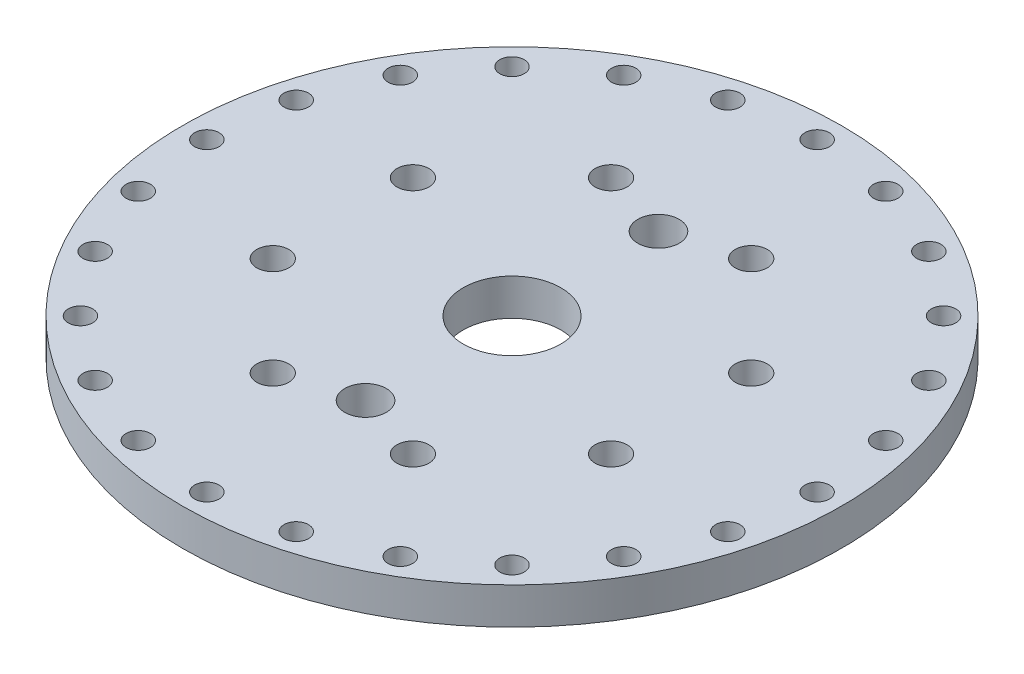
SolidWorks part; units mm, degrees
material "Alloy Steel"
ref_plane "Front Plane" through (0, 0, 0) normal (0, 0, 1) x (1, 0, 0)
ref_plane "Top Plane" through (0, 0, 0) normal (0, 1, 0) x (1, 0, 0)
ref_plane "Right Plane" through (0, 0, 0) normal (1, 0, 0) x (0, 0, -1)
sketch "Sketch5" plane through (0, 0, 0) normal (0, 1, 0) x (1, 0, 0)
  line L0 (87.3464, 51.4964) -> (89.0397, 50.8872)
  line L1 (89.0397, 50.8872) -> (90.7249, 50.062)
  line L2 (90.7249, 50.062) -> (90.7249, 49.095)
  line L3 (90.7249, 49.095) -> (89.0397, 48.2698)
  line L4 (89.0397, 48.2698) -> (87.3464, 47.6606)
  line L5 (87.3464, 47.6606) -> (87.2693, 46.4828)
  line L6 (87.2693, 46.4828) -> (88.8685, 45.6578)
  line L7 (88.8685, 45.6578) -> (90.4317, 44.6196)
  line L8 (90.4317, 44.6196) -> (90.3054, 43.6609)
  line L9 (90.3054, 43.6609) -> (88.5268, 43.0627)
  line L10 (88.5268, 43.0627) -> (86.7686, 42.6797)
  line L11 (86.7686, 42.6797) -> (86.5383, 41.5221)
  line L12 (86.5383, 41.5221) -> (88.0162, 40.4955)
  line L13 (88.0162, 40.4955) -> (89.4304, 39.2621)
  line L14 (89.4304, 39.2621) -> (89.1801, 38.328)
  line L15 (89.1801, 38.328) -> (87.3386, 37.9672)
  line L16 (87.3386, 37.9672) -> (85.5454, 37.8169)
  line L17 (85.5454, 37.8169) -> (85.1661, 36.6994)
  line L18 (85.1661, 36.6994) -> (86.4974, 35.4884)
  line L19 (86.4974, 35.4884) -> (87.7385, 34.0811)
  line L20 (87.7385, 34.0811) -> (87.3685, 33.1877)
  line L21 (87.3685, 33.1877) -> (85.4956, 33.0702)
  line L22 (85.4956, 33.0702) -> (83.6981, 33.1553)
  line L23 (83.6981, 33.1553) -> (83.1762, 32.0968)
  line L24 (83.1762, 32.0968) -> (84.3379, 30.7226)
  line L25 (84.3379, 30.7226) -> (85.3848, 29.1653)
  line L26 (85.3848, 29.1653) -> (84.9013, 28.3278)
  line L27 (84.9013, 28.3278) -> (83.0292, 28.4557)
  line L28 (83.0292, 28.4557) -> (81.2581, 28.7747)
  line L29 (81.2581, 28.7747) -> (80.6024, 27.7935)
  line L30 (80.6024, 27.7935) -> (81.575, 26.2794)
  line L31 (81.575, 26.2794) -> (82.4096, 24.5987)
  line L32 (82.4096, 24.5987) -> (81.821, 23.8315)
  line L33 (81.821, 23.8315) -> (79.9815, 24.2028)
  line L34 (79.9815, 24.2028) -> (78.2673, 24.7502)
  line L35 (78.2673, 24.7502) -> (77.4891, 23.8628)
  line L36 (77.4891, 23.8628) -> (78.2556, 22.2348)
  line L37 (78.2556, 22.2348) -> (78.8638, 20.4595)
  line L38 (78.8638, 20.4595) -> (78.18, 19.7757)
  line L39 (78.18, 19.7757) -> (76.4047, 20.3839)
  line L40 (76.4047, 20.3839) -> (74.7767, 21.1504)
  line L41 (74.7767, 21.1504) -> (73.8893, 20.3722)
  line L42 (73.8893, 20.3722) -> (74.4368, 18.658)
  line L43 (74.4368, 18.658) -> (74.808, 16.8186)
  line L44 (74.808, 16.8186) -> (74.0408, 16.2299)
  line L45 (74.0408, 16.2299) -> (72.3602, 17.0645)
  line L46 (72.3602, 17.0645) -> (70.846, 18.0371)
  line L47 (70.846, 18.0371) -> (69.8648, 17.3814)
  line L48 (69.8648, 17.3814) -> (70.1838, 15.6104)
  line L49 (70.1838, 15.6104) -> (70.3117, 13.7382)
  line L50 (70.3117, 13.7382) -> (69.4742, 13.2547)
  line L51 (69.4742, 13.2547) -> (67.9169, 14.3016)
  line L52 (67.9169, 14.3016) -> (66.5427, 15.4634)
  line L53 (66.5427, 15.4634) -> (65.4842, 14.9415)
  line L54 (65.4842, 14.9415) -> (65.5693, 13.1439)
  line L55 (65.5693, 13.1439) -> (65.4518, 11.271)
  line L56 (65.4518, 11.271) -> (64.5584, 10.901)
  line L57 (64.5584, 10.901) -> (63.1511, 12.1422)
  line L58 (63.1511, 12.1422) -> (61.9401, 13.4734)
  line L59 (61.9401, 13.4734) -> (60.8226, 13.0941)
  line L60 (60.8226, 13.0941) -> (60.6724, 11.3009)
  line L61 (60.6724, 11.3009) -> (60.3115, 9.4594)
  line L62 (60.3115, 9.4594) -> (59.3774, 9.2091)
  line L63 (59.3774, 9.2091) -> (58.144, 10.6233)
  line L64 (58.144, 10.6233) -> (57.1174, 12.1012)
  line L65 (57.1174, 12.1012) -> (55.9598, 11.8709)
  line L66 (55.9598, 11.8709) -> (55.5768, 10.1127)
  line L67 (55.5768, 10.1127) -> (54.9786, 8.3341)
  line L68 (54.9786, 8.3341) -> (54.0199, 8.2078)
  line L69 (54.0199, 8.2078) -> (52.9817, 9.771)
  line L70 (52.9817, 9.771) -> (52.1567, 11.3702)
  line L71 (52.1567, 11.3702) -> (50.979, 11.2931)
  line L72 (50.979, 11.2931) -> (50.3698, 9.5998)
  line L73 (50.3698, 9.5998) -> (49.5446, 7.9146)
  line L74 (49.5446, 7.9146) -> (48.5775, 7.9146)
  line L75 (48.5775, 7.9146) -> (47.7523, 9.5998)
  line L76 (47.7523, 9.5998) -> (47.1431, 11.2931)
  line L77 (47.1431, 11.2931) -> (45.9654, 11.3702)
  line L78 (45.9654, 11.3702) -> (45.1403, 9.771)
  line L79 (45.1403, 9.771) -> (44.1021, 8.2078)
  line L80 (44.1021, 8.2078) -> (43.1434, 8.3341)
  line L81 (43.1434, 8.3341) -> (42.5452, 10.1127)
  line L82 (42.5452, 10.1127) -> (42.1622, 11.8709)
  line L83 (42.1622, 11.8709) -> (41.0046, 12.1012)
  line L84 (41.0046, 12.1012) -> (39.978, 10.6233)
  line L85 (39.978, 10.6233) -> (38.7447, 9.2091)
  line L86 (38.7447, 9.2091) -> (37.8106, 9.4594)
  line L87 (37.8106, 9.4594) -> (37.4497, 11.3009)
  line L88 (37.4497, 11.3009) -> (37.2994, 13.0941)
  line L89 (37.2994, 13.0941) -> (36.1819, 13.4734)
  line L90 (36.1819, 13.4734) -> (34.9709, 12.1422)
  line L91 (34.9709, 12.1422) -> (33.5636, 10.901)
  line L92 (33.5636, 10.901) -> (32.6702, 11.271)
  line L93 (32.6702, 11.271) -> (32.5527, 13.1439)
  line L94 (32.5527, 13.1439) -> (32.6378, 14.9415)
  line L95 (32.6378, 14.9415) -> (31.5793, 15.4634)
  line L96 (31.5793, 15.4634) -> (30.2051, 14.3016)
  line L97 (30.2051, 14.3016) -> (28.6478, 13.2547)
  line L98 (28.6478, 13.2547) -> (27.8103, 13.7382)
  line L99 (27.8103, 13.7382) -> (27.9382, 15.6104)
  line L100 (27.9382, 15.6104) -> (28.2572, 17.3814)
  line L101 (28.2572, 17.3814) -> (27.276, 18.0371)
  line L102 (27.276, 18.0371) -> (25.7619, 17.0645)
  line L103 (25.7619, 17.0645) -> (24.0812, 16.2299)
  line L104 (24.0812, 16.2299) -> (23.314, 16.8186)
  line L105 (23.314, 16.8186) -> (23.6853, 18.658)
  line L106 (23.6853, 18.658) -> (24.2327, 20.3722)
  line L107 (24.2327, 20.3722) -> (23.3453, 21.1504)
  line L108 (23.3453, 21.1504) -> (21.7173, 20.3839)
  line L109 (21.7173, 20.3839) -> (19.9421, 19.7757)
  line L110 (19.9421, 19.7757) -> (19.2582, 20.4595)
  line L111 (19.2582, 20.4595) -> (19.8664, 22.2348)
  line L112 (19.8664, 22.2348) -> (20.6329, 23.8628)
  line L113 (20.6329, 23.8628) -> (19.8547, 24.7502)
  line L114 (19.8547, 24.7502) -> (18.1405, 24.2028)
  line L115 (18.1405, 24.2028) -> (16.3011, 23.8315)
  line L116 (16.3011, 23.8315) -> (15.7124, 24.5987)
  line L117 (15.7124, 24.5987) -> (16.547, 26.2794)
  line L118 (16.547, 26.2794) -> (17.5196, 27.7935)
  line L119 (17.5196, 27.7935) -> (16.8639, 28.7747)
  line L120 (16.8639, 28.7747) -> (15.0929, 28.4557)
  line L121 (15.0929, 28.4557) -> (13.2207, 28.3278)
  line L122 (13.2207, 28.3278) -> (12.7372, 29.1653)
  line L123 (12.7372, 29.1653) -> (13.7841, 30.7226)
  line L124 (13.7841, 30.7226) -> (14.9459, 32.0968)
  line L125 (14.9459, 32.0968) -> (14.424, 33.1553)
  line L126 (14.424, 33.1553) -> (12.6264, 33.0702)
  line L127 (12.6264, 33.0702) -> (10.7535, 33.1877)
  line L128 (10.7535, 33.1877) -> (10.3835, 34.0811)
  line L129 (10.3835, 34.0811) -> (11.6247, 35.4884)
  line L130 (11.6247, 35.4884) -> (12.9559, 36.6994)
  line L131 (12.9559, 36.6994) -> (12.5766, 37.8169)
  line L132 (12.5766, 37.8169) -> (10.7834, 37.9672)
  line L133 (10.7834, 37.9672) -> (8.9419, 38.328)
  line L134 (8.9419, 38.328) -> (8.6916, 39.2621)
  line L135 (8.6916, 39.2621) -> (10.1058, 40.4955)
  line L136 (10.1058, 40.4955) -> (11.5837, 41.5221)
  line L137 (11.5837, 41.5221) -> (11.3534, 42.6797)
  line L138 (11.3534, 42.6797) -> (9.5952, 43.0627)
  line L139 (9.5952, 43.0627) -> (7.8167, 43.6609)
  line L140 (7.8167, 43.6609) -> (7.6903, 44.6196)
  line L141 (7.6903, 44.6196) -> (9.2536, 45.6578)
  line L142 (9.2536, 45.6578) -> (10.8528, 46.4828)
  line L143 (10.8528, 46.4828) -> (10.7757, 47.6606)
  line L144 (10.7757, 47.6606) -> (9.0823, 48.2698)
  line L145 (9.0823, 48.2698) -> (7.3971, 49.095)
  line L146 (7.3971, 49.095) -> (7.3971, 50.062)
  line L147 (7.3971, 50.062) -> (9.0823, 50.8872)
  line L148 (9.0823, 50.8872) -> (10.7757, 51.4964)
  line L149 (10.7757, 51.4964) -> (10.8528, 52.6742)
  line L150 (10.8528, 52.6742) -> (9.2536, 53.4992)
  line L151 (9.2536, 53.4992) -> (7.6903, 54.5374)
  line L152 (7.6903, 54.5374) -> (7.8167, 55.4961)
  line L153 (7.8167, 55.4961) -> (9.5952, 56.0943)
  line L154 (9.5952, 56.0943) -> (11.3534, 56.4773)
  line L155 (11.3534, 56.4773) -> (11.5837, 57.6349)
  line L156 (11.5837, 57.6349) -> (10.1058, 58.6615)
  line L157 (10.1058, 58.6615) -> (8.6916, 59.8949)
  line L158 (8.6916, 59.8949) -> (8.9419, 60.829)
  line L159 (8.9419, 60.829) -> (10.7834, 61.1898)
  line L160 (10.7834, 61.1898) -> (12.5766, 61.3401)
  line L161 (12.5766, 61.3401) -> (12.9559, 62.4576)
  line L162 (12.9559, 62.4576) -> (11.6247, 63.6686)
  line L163 (11.6247, 63.6686) -> (10.3835, 65.0759)
  line L164 (10.3835, 65.0759) -> (10.7535, 65.9693)
  line L165 (10.7535, 65.9693) -> (12.6264, 66.0868)
  line L166 (12.6264, 66.0868) -> (14.424, 66.0017)
  line L167 (14.424, 66.0017) -> (14.9459, 67.0602)
  line L168 (14.9459, 67.0602) -> (13.7841, 68.4344)
  line L169 (13.7841, 68.4344) -> (12.7372, 69.9917)
  line L170 (12.7372, 69.9917) -> (13.2207, 70.8292)
  line L171 (13.2207, 70.8292) -> (15.0929, 70.7013)
  line L172 (15.0929, 70.7013) -> (16.8639, 70.3823)
  line L173 (16.8639, 70.3823) -> (17.5196, 71.3635)
  line L174 (17.5196, 71.3635) -> (16.547, 72.8776)
  line L175 (16.547, 72.8776) -> (15.7124, 74.5583)
  line L176 (15.7124, 74.5583) -> (16.3011, 75.3255)
  line L177 (16.3011, 75.3255) -> (18.1405, 74.9542)
  line L178 (18.1405, 74.9542) -> (19.8547, 74.4068)
  line L179 (19.8547, 74.4068) -> (20.6329, 75.2942)
  line L180 (20.6329, 75.2942) -> (19.8664, 76.9222)
  line L181 (19.8664, 76.9222) -> (19.2582, 78.6975)
  line L182 (19.2582, 78.6975) -> (19.9421, 79.3813)
  line L183 (19.9421, 79.3813) -> (21.7173, 78.7731)
  line L184 (21.7173, 78.7731) -> (23.3453, 78.0066)
  line L185 (23.3453, 78.0066) -> (24.2327, 78.7848)
  line L186 (24.2327, 78.7848) -> (23.6853, 80.499)
  line L187 (23.6853, 80.499) -> (23.314, 82.3384)
  line L188 (23.314, 82.3384) -> (24.0812, 82.9271)
  line L189 (24.0812, 82.9271) -> (25.7619, 82.0925)
  line L190 (25.7619, 82.0925) -> (27.276, 81.1199)
  line L191 (27.276, 81.1199) -> (28.2572, 81.7756)
  line L192 (28.2572, 81.7756) -> (27.9382, 83.5466)
  line L193 (27.9382, 83.5466) -> (27.8103, 85.4188)
  line L194 (27.8103, 85.4188) -> (28.6478, 85.9023)
  line L195 (28.6478, 85.9023) -> (30.2051, 84.8554)
  line L196 (30.2051, 84.8554) -> (31.5793, 83.6936)
  line L197 (31.5793, 83.6936) -> (32.6378, 84.2155)
  line L198 (32.6378, 84.2155) -> (32.5527, 86.0131)
  line L199 (32.5527, 86.0131) -> (32.6702, 87.886)
  line L200 (32.6702, 87.886) -> (33.5636, 88.256)
  line L201 (33.5636, 88.256) -> (34.9709, 87.0148)
  line L202 (34.9709, 87.0148) -> (36.1819, 85.6836)
  line L203 (36.1819, 85.6836) -> (37.2994, 86.0629)
  line L204 (37.2994, 86.0629) -> (37.4497, 87.8561)
  line L205 (37.4497, 87.8561) -> (37.8106, 89.6976)
  line L206 (37.8106, 89.6976) -> (38.7447, 89.9479)
  line L207 (38.7447, 89.9479) -> (39.978, 88.5337)
  line L208 (39.978, 88.5337) -> (41.0046, 87.0558)
  line L209 (41.0046, 87.0558) -> (42.1622, 87.2861)
  line L210 (42.1622, 87.2861) -> (42.5452, 89.0443)
  line L211 (42.5452, 89.0443) -> (43.1434, 90.8228)
  line L212 (43.1434, 90.8228) -> (44.1021, 90.9492)
  line L213 (44.1021, 90.9492) -> (45.1403, 89.386)
  line L214 (45.1403, 89.386) -> (45.9654, 87.7868)
  line L215 (45.9654, 87.7868) -> (47.1431, 87.8639)
  line L216 (47.1431, 87.8639) -> (47.7523, 89.5572)
  line L217 (47.7523, 89.5572) -> (48.5775, 91.2424)
  line L218 (48.5775, 91.2424) -> (49.5446, 91.2424)
  line L219 (49.5446, 91.2424) -> (50.3698, 89.5572)
  line L220 (50.3698, 89.5572) -> (50.979, 87.8639)
  line L221 (50.979, 87.8639) -> (52.1567, 87.7868)
  line L222 (52.1567, 87.7868) -> (52.9817, 89.386)
  line L223 (52.9817, 89.386) -> (54.0199, 90.9492)
  line L224 (54.0199, 90.9492) -> (54.9786, 90.8228)
  line L225 (54.9786, 90.8228) -> (55.5768, 89.0443)
  line L226 (55.5768, 89.0443) -> (55.9598, 87.2861)
  line L227 (55.9598, 87.2861) -> (57.1174, 87.0558)
  line L228 (57.1174, 87.0558) -> (58.144, 88.5337)
  line L229 (58.144, 88.5337) -> (59.3774, 89.9479)
  line L230 (59.3774, 89.9479) -> (60.3115, 89.6976)
  line L231 (60.3115, 89.6976) -> (60.6724, 87.8561)
  line L232 (60.6724, 87.8561) -> (60.8226, 86.0629)
  line L233 (60.8226, 86.0629) -> (61.9401, 85.6836)
  line L234 (61.9401, 85.6836) -> (63.1511, 87.0148)
  line L235 (63.1511, 87.0148) -> (64.5584, 88.256)
  line L236 (64.5584, 88.256) -> (65.4518, 87.886)
  line L237 (65.4518, 87.886) -> (65.5693, 86.0131)
  line L238 (65.5693, 86.0131) -> (65.4842, 84.2155)
  line L239 (65.4842, 84.2155) -> (66.5427, 83.6936)
  line L240 (66.5427, 83.6936) -> (67.9169, 84.8554)
  line L241 (67.9169, 84.8554) -> (69.4742, 85.9023)
  line L242 (69.4742, 85.9023) -> (70.3117, 85.4188)
  line L243 (70.3117, 85.4188) -> (70.1838, 83.5466)
  line L244 (70.1838, 83.5466) -> (69.8648, 81.7756)
  line L245 (69.8648, 81.7756) -> (70.846, 81.1199)
  line L246 (70.846, 81.1199) -> (72.3602, 82.0925)
  line L247 (72.3602, 82.0925) -> (74.0408, 82.9271)
  line L248 (74.0408, 82.9271) -> (74.808, 82.3384)
  line L249 (74.808, 82.3384) -> (74.4368, 80.499)
  line L250 (74.4368, 80.499) -> (73.8893, 78.7848)
  line L251 (73.8893, 78.7848) -> (74.7767, 78.0066)
  line L252 (74.7767, 78.0066) -> (76.4047, 78.7731)
  line L253 (76.4047, 78.7731) -> (78.18, 79.3813)
  line L254 (78.18, 79.3813) -> (78.8638, 78.6975)
  line L255 (78.8638, 78.6975) -> (78.2556, 76.9222)
  line L256 (78.2556, 76.9222) -> (77.4891, 75.2942)
  line L257 (77.4891, 75.2942) -> (78.2673, 74.4068)
  line L258 (78.2673, 74.4068) -> (79.9815, 74.9542)
  line L259 (79.9815, 74.9542) -> (81.821, 75.3255)
  line L260 (81.821, 75.3255) -> (82.4096, 74.5583)
  line L261 (82.4096, 74.5583) -> (81.575, 72.8776)
  line L262 (81.575, 72.8776) -> (80.6024, 71.3635)
  line L263 (80.6024, 71.3635) -> (81.2581, 70.3823)
  line L264 (81.2581, 70.3823) -> (83.0292, 70.7013)
  line L265 (83.0292, 70.7013) -> (84.9013, 70.8292)
  line L266 (84.9013, 70.8292) -> (85.3848, 69.9917)
  line L267 (85.3848, 69.9917) -> (84.3379, 68.4344)
  line L268 (84.3379, 68.4344) -> (83.1762, 67.0602)
  line L269 (83.1762, 67.0602) -> (83.6981, 66.0017)
  line L270 (83.6981, 66.0017) -> (85.4956, 66.0868)
  line L271 (85.4956, 66.0868) -> (87.3685, 65.9693)
  line L272 (87.3685, 65.9693) -> (87.7385, 65.0759)
  line L273 (87.7385, 65.0759) -> (86.4974, 63.6686)
  line L274 (86.4974, 63.6686) -> (85.1661, 62.4576)
  line L275 (85.1661, 62.4576) -> (85.5454, 61.3401)
  line L276 (85.5454, 61.3401) -> (87.3386, 61.1898)
  line L277 (87.3386, 61.1898) -> (89.1801, 60.829)
  line L278 (89.1801, 60.829) -> (89.4304, 59.8949)
  line L279 (89.4304, 59.8949) -> (88.0162, 58.6615)
  line L280 (88.0162, 58.6615) -> (86.5383, 57.6349)
  line L281 (86.5383, 57.6349) -> (86.7686, 56.4773)
  line L282 (86.7686, 56.4773) -> (88.5268, 56.0943)
  line L283 (88.5268, 56.0943) -> (90.3054, 55.4961)
  line L284 (90.3054, 55.4961) -> (90.4317, 54.5374)
  line L285 (90.4317, 54.5374) -> (88.8685, 53.4992)
  line L286 (88.8685, 53.4992) -> (87.2693, 52.6742)
  line L287 (87.2693, 52.6742) -> (87.3464, 51.4964)
  line L288 (49.061, 91.2424) -> (49.061, 7.9146) construction
  line L289 (7.3971, 49.5785) -> (90.7249, 49.5785) construction
  point P292 (49.061, 49.5785)
sketch "Sketch6" plane through (0, 0, 0) normal (0, 1, 0) x (1, 0, 0)
  line L0 (49.061, 91.2424) -> (49.061, 7.9146) construction
  circle A0 centre (49.061, 49.5785) radius 4
  dimension "D1" = 8
sketch "Sketch7" plane through (0, 0, 0) normal (0, 1, 0) x (1, 0, 0)
  line L0 (49.061, 91.2424) -> (49.061, 7.9146) construction
  line L1 (25.4921, 49.5785) -> (64.6594, 49.5785) construction
  line L2 (7.3971, 49.5785) -> (90.7249, 49.5785) construction
  circle A0 centre (49.061, 61.5785) radius 1.7
  circle A1 centre (49.061, 37.5785) radius 1.7
  dimension "D2" = 3.4
  dimension "D1" = 12
sketch "Sketch8" plane through (0, 0, 0) normal (0, 1, 0) x (1, 0, 0)
  line L0 (7.3971, 49.5785) -> (90.7249, 49.5785) construction
  circle A0 centre (49.061, 49.5785) radius 27
  dimension "D1" = 54
sketch "Sketch9" plane through (0, 0, 0) normal (0, 1, 0) x (1, 0, 0)
  line L0 (49.061, 91.2424) -> (49.061, 7.9146) construction
  line L1 (49.061, 74.5785) -> (49.061, 76.5785) construction
  circle A0 centre (49.061, 74.5785) radius 1
  circle A1 centre (49.061, 49.5785) radius 27 construction
  circle A2 centre (55.5315, 73.7266) radius 1
  circle A3 centre (61.561, 71.2291) radius 1
  circle A4 centre (66.7387, 67.2562) radius 1
  circle A5 centre (70.7116, 62.0785) radius 1
  circle A6 centre (73.2092, 56.049) radius 1
  circle A7 centre (74.061, 49.5785) radius 1
  circle A8 centre (73.2092, 43.108) radius 1
  circle A9 centre (70.7116, 37.0785) radius 1
  circle A10 centre (66.7387, 31.9008) radius 1
  circle A11 centre (61.561, 27.9279) radius 1
  circle A12 centre (55.5315, 25.4304) radius 1
  circle A13 centre (49.061, 24.5785) radius 1
  circle A14 centre (42.5905, 25.4304) radius 1
  circle A15 centre (36.561, 27.9279) radius 1
  circle A16 centre (31.3833, 31.9008) radius 1
  circle A17 centre (27.4104, 37.0785) radius 1
  circle A18 centre (24.9129, 43.108) radius 1
  circle A19 centre (24.061, 49.5785) radius 1
  circle A20 centre (24.9129, 56.049) radius 1
  circle A21 centre (27.4104, 62.0785) radius 1
  circle A22 centre (31.3833, 67.2562) radius 1
  circle A23 centre (36.561, 71.2291) radius 1
  circle A24 centre (42.5905, 73.7266) radius 1
  point P55 (49.061, 49.5785)
  dimension "D1" = 2
  dimension "D2" = 2
  dimension "D3" = 24
extrude "Boss-Extrude1" add sketch "Sketch8" along normal blind 3
extrude "Boss-Extrude2" [suppressed] add sketch "Sketch5" along normal up to surface (4 mm away) up to face at (49.061, 3, -22.5785)
extrude "Cut-Extrude1" cut sketch "Sketch6" along normal up to next
extrude "Cut-Extrude2" cut sketch "Sketch7" along normal up to next
extrude "Cut-Extrude3" cut sketch "Sketch9" along normal up to next
ref_axis "Axis1" [suppressed] through (49.061, 4, -49.5785) along (0, -1, 0)
sketch "Sketch11" plane through (0, 0, 0) normal (0, 1, 0) x (1, 0, 0)
  line L0 (59.3935, 74.5232) -> (49.061, 49.5785) construction
  line L1 (49.061, 49.5785) -> (49.061, 76.5785) construction
  circle A0 centre (49.061, 49.5785) radius 27 construction
  circle A1 centre (54.8013, 63.4367) radius 1.3125
  circle A2 centre (62.9192, 55.3188) radius 1.3125
  circle A3 centre (62.9192, 43.8382) radius 1.3125
  circle A4 centre (54.8013, 35.7203) radius 1.3125
  circle A5 centre (43.3208, 35.7203) radius 1.3125
  circle A6 centre (35.2028, 43.8382) radius 1.3125
  circle A7 centre (35.2028, 55.3188) radius 1.3125
  circle A8 centre (43.3208, 63.4367) radius 1.3125
  point P0 (49.061, 49.5785)
  point P36 (49.061, 49.5785)
  dimension "D2" = 2.625
  dimension "D1" = 15
  dimension "D4" = 22.5
  dimension "D3" = 8
extrude "Cut-Extrude4" cut sketch "Sketch11" along normal up to next
